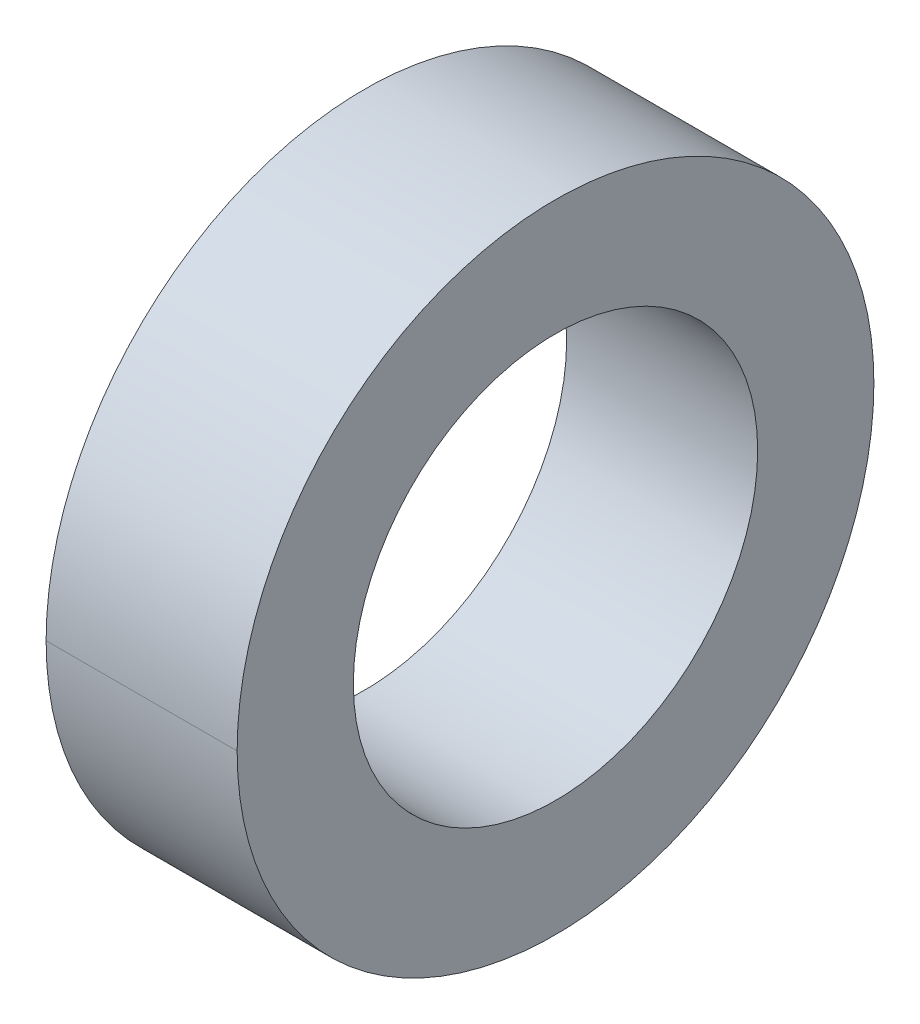
SolidWorks part; units mm, degrees
material "Acrylic (Medium-high impact)"
ref_plane "Alzado" through (0, 0, 0) normal (0, 0, 1) x (1, 0, 0)
ref_plane "Planta" through (0, 0, 0) normal (0, 1, 0) x (1, 0, 0)
ref_plane "Vista lateral" through (0, 0, 0) normal (1, 0, 0) x (0, 0, -1)
sketch "Sketch1" plane through (0, 0, 0) normal (1, 0, 0) x (0, 0, -1)
  line L1 (-5, 5) -> (5, 5)
  line L2 (-5, 5) -> (-5, -5)
  line L3 (-5, -5) -> (5, -5)
  line L4 (5, 5) -> (5, -5)
  line L5 (-5, 5) -> (5, -5) construction
  line L6 (-5, -5) -> (5, 5) construction
  circle A0 centre (0, 0) radius 2.5
  point P0 (0, 0)
  dimension "D1" = 10
  dimension "D2" = 10
extrude "Boss-Extrude1" add sketch "Sketch1" along normal blind 3 contours L1 L4 L3 L2
sketch "Sketch2" plane through (0, 0, 0) normal (-1, 0, 0) x (0, 0, 1)
  circle A0 centre (0, 0) radius 3.175
extrude "Cut-Extrude1" cut sketch "Sketch2" against normal blind 10
fillet "Fillet1" 2 edges at (1.5, 5, -5) (1.5, 5, 5) type full round first side face at (1.5, 0, -5) second side face at (1.5, 0, 5) middle face at (1.5, 5, 0)
fillet "Fillet2" 2 edges at (1.5, -5, -5) (1.5, -5, 5) type full round first side face at (1.5, -2.5, -5) second side face at (1.5, -2.5, 5) middle face at (1.5, -5, 0)
